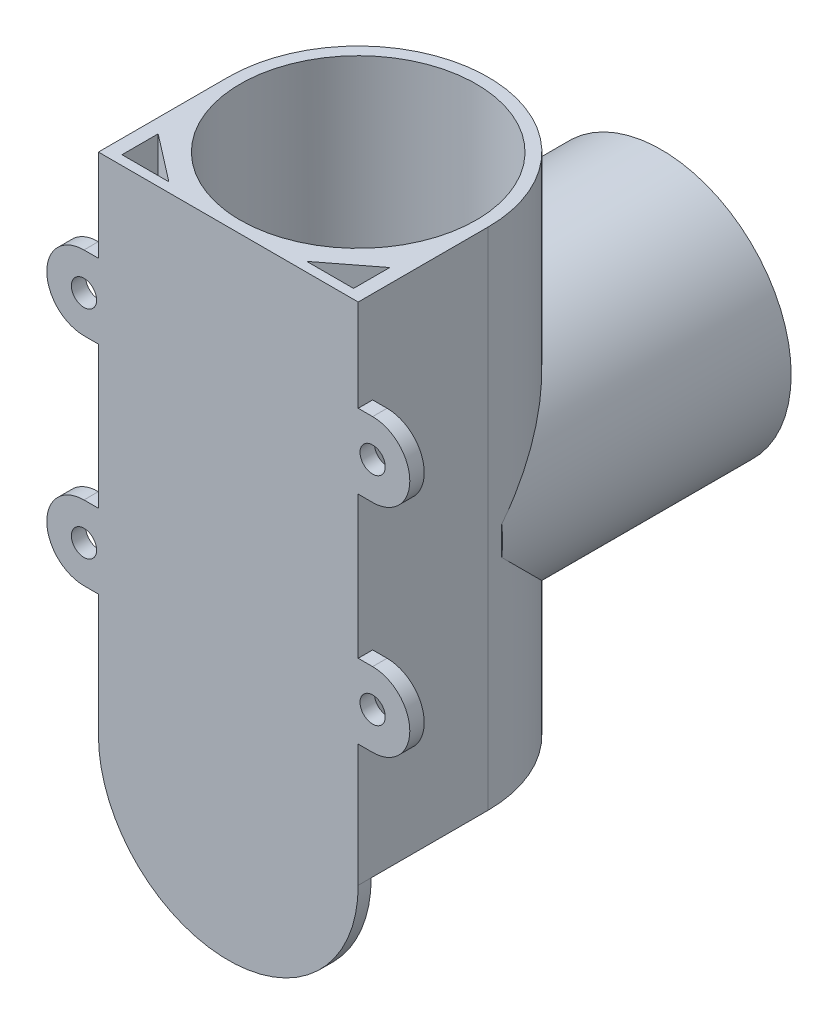
SolidWorks part; units mm, degrees
ref_plane "Front Plane" through (0, 0, 0) normal (0, 0, 1) x (1, 0, 0)
ref_plane "Top Plane" through (0, 0, 0) normal (0, 1, 0) x (1, 0, 0)
ref_plane "Right Plane" through (0, 0, 0) normal (1, 0, 0) x (0, 0, -1)
sketch "Sketch1" plane through (0, 0, 0) normal (0, 1, 0) x (1, 0, 0)
  line L0 (18, -18) -> (-18, -18)
  line L1 (-18, -18) -> (-18, 0)
  line L2 (0, -55) -> (0, 55) construction
  line L3 (18, -18) -> (18, 0)
  line L4 (-16.0462, -16.691) -> (-9.5492, -16.691)
  line L5 (-9.5492, -16.691) -> (-16.0462, -11.6765)
  line L6 (-16.0462, -11.6765) -> (-16.0462, -16.691)
  line L7 (16.0462, -16.691) -> (9.5492, -16.691)
  line L8 (9.5492, -16.691) -> (16.0462, -11.6765)
  line L9 (16.0462, -11.6765) -> (16.0462, -16.691)
  arc A0 (18, 0) -> (-18, 0) centre (0, 0) ccw
  circle A1 centre (0, 0) radius 16.35
  point P10 (0, -18)
  dimension "D1" = 36
  dimension "D2" = 1.65
extrude "Boss-Extrude1" add sketch "Sketch1" along normal blind 70
sketch "Sketch2" plane through (0, 0, 18) normal (0, 0, 1) x (1, 0, 0)
  line L0 (0, -55) -> (0, 55) construction
  circle A0 centre (0, 31.2916) radius 15.24
  dimension "D1" = 30.48
sketch "Sketch4" plane through (0, 0, 18) normal (0, 0, 1) x (1, 0, 0)
  line L0 (-18, 0) -> (18, 0)
  line L1 (-18, 70) -> (-18, 0) construction
  arc A0 (-18, 0) -> (18, 0) centre (0, 0) ccw
extrude "Boss-Extrude3" add sketch "Sketch4" against normal blind 1.8
sketch "Sketch5" plane through (0, 0, 0) normal (1, 0, 0) x (0, 0, -1)
  line L0 (-14.2, 0) -> (-18, -15.9552)
  line L1 (55, 0) -> (-55, 0) construction
  line L2 (-18, 0) -> (-18, -18) construction
  line L3 (-18, -15.9552) -> (-16.2, -18)
  line L4 (-16.2, -18) -> (-14.2, 0)
sketch "Sketch6" plane through (0, 0, 18) normal (0, 0, 1) x (1, 0, 0)
  line L0 (0, -19.8) -> (0, 19.8) construction
  line L5 (-12.2959, 27.2473) -> (-12.2959, 16.9473)
  line L6 (-20, 46.9468) -> (-12.2959, 46.9468)
  line L7 (-20, 57.2478) -> (-12.2959, 57.2478)
  line L8 (-20, 27.2473) -> (-12.2959, 27.2473)
  line L9 (-20, 16.9473) -> (-12.2959, 16.9473)
  line L10 (9.1712, 57.2478) -> (20, 57.2478)
  line L12 (9.1712, 57.2478) -> (9.1712, 46.9468)
  line L14 (-12.2959, 57.2478) -> (-12.2959, 46.9468)
  line L15 (9.1712, 27.2473) -> (9.1712, 16.9473)
  line L19 (9.1712, 46.9468) -> (20, 46.9468)
  line L20 (9.1712, 27.2473) -> (20, 27.2473)
  line L21 (9.1712, 16.9473) -> (20, 16.9473)
  circle A0 centre (-20, 22.0973) radius 1.75
  circle A1 centre (-20, 52.0973) radius 1.75
  circle A2 centre (20, 52.0973) radius 1.75
  circle A3 centre (20, 22.0973) radius 1.75
  arc A4 (-20, 57.2478) -> (-20, 46.9468) centre (-20, 52.0973) ccw
  arc A5 (-20, 27.2473) -> (-20, 16.9473) centre (-20, 22.0973) ccw
  arc A6 (20, 27.2473) -> (20, 16.9473) centre (20, 22.0973) cw
  arc A7 (20, 57.2478) -> (20, 46.9468) centre (20, 52.0973) cw
  point P0 (0, 48.9125)
  point P2 (-3.0515, 44.9806)
  dimension "D5" = 3.5
  dimension "D6" = 3.5
  dimension "D1" = 10.3
  dimension "D8" = 3.5
  dimension "D9" = 3.5
  dimension "D2" = 20
  dimension "D3" = 30
  dimension "D4" = 20
  dimension "D7" = 20
extrude "Boss-Extrude4" add sketch "Sketch6" against normal blind 2
sketch "Sketch8" plane through (0, 0, 0) normal (0, 0, 1) x (1, 0, 0)
  circle A0 centre (0, 31.2916) radius 18
  dimension "D1" = 36
extrude "Cut-Extrude4" cut sketch "Sketch2" against normal blind 90 from offset 10 offset against normal yes
extrude "Extrude-Thin1" add sketch "Sketch8" against normal blind 40 from offset 2 thin offset against normal yes thin type one direction reverse wall 2
sketch "Sketch9" plane through (0, 0, 0) normal (0, 1, 0) x (1, 0, 0)
  circle A1 centre (0, 0) radius 16.35
  point P10 (0, -18)
extrude "Cut-Extrude5" cut sketch "Sketch9" against normal through all both and the other way through all
